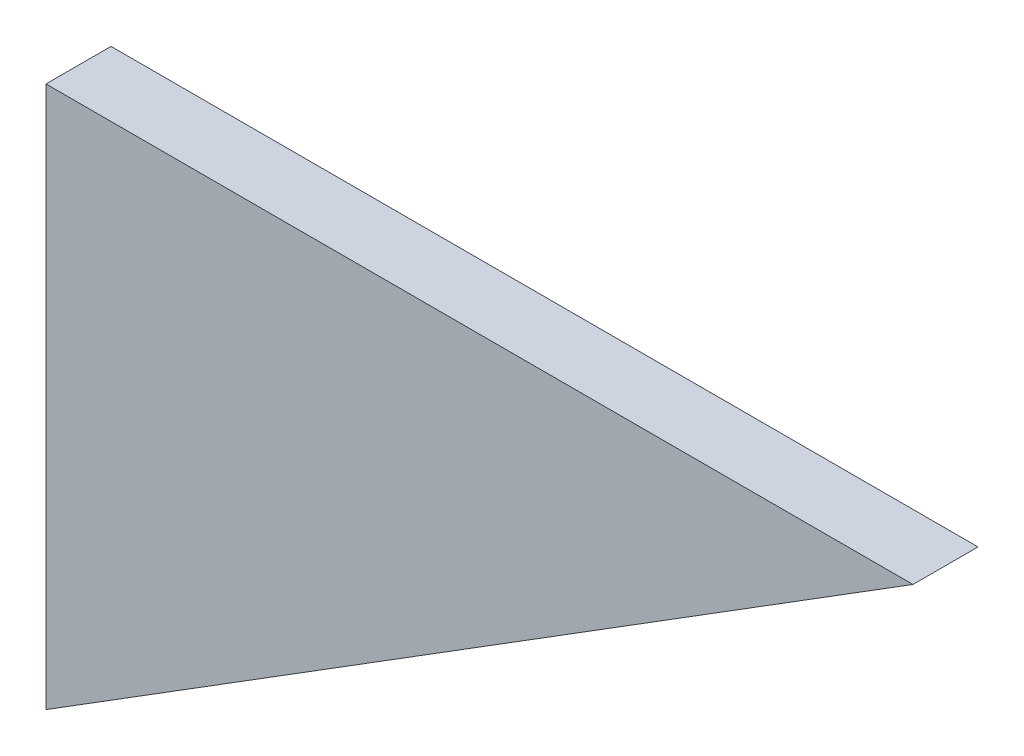
SolidWorks part; units mm, degrees
material "Клен"
ref_plane "Спереди" through (0, 0, 0) normal (0, 0, 1) x (1, 0, 0)
ref_plane "Сверху" through (0, 0, 0) normal (0, 1, 0) x (1, 0, 0)
ref_plane "Справа" through (0, 0, 0) normal (1, 0, 0) x (0, 0, -1)
sketch "Эскиз1" plane through (0, 0, 0) normal (0, 0, 1) x (1, 0, 0)
  line L5 (6, -293.8462) -> (6, -343.8462)
  line L7 (6, -343.8462) -> (86, -293.8462)
  line L9 (86, -293.8462) -> (6, -293.8462)
  point P2 (0, 0)
  dimension "D1" = 50
  dimension "D2" = 80
extrude "Бобышка-Вытянуть1" add sketch "Эскиз1" against normal blind 6 contours L7 L9 L5
